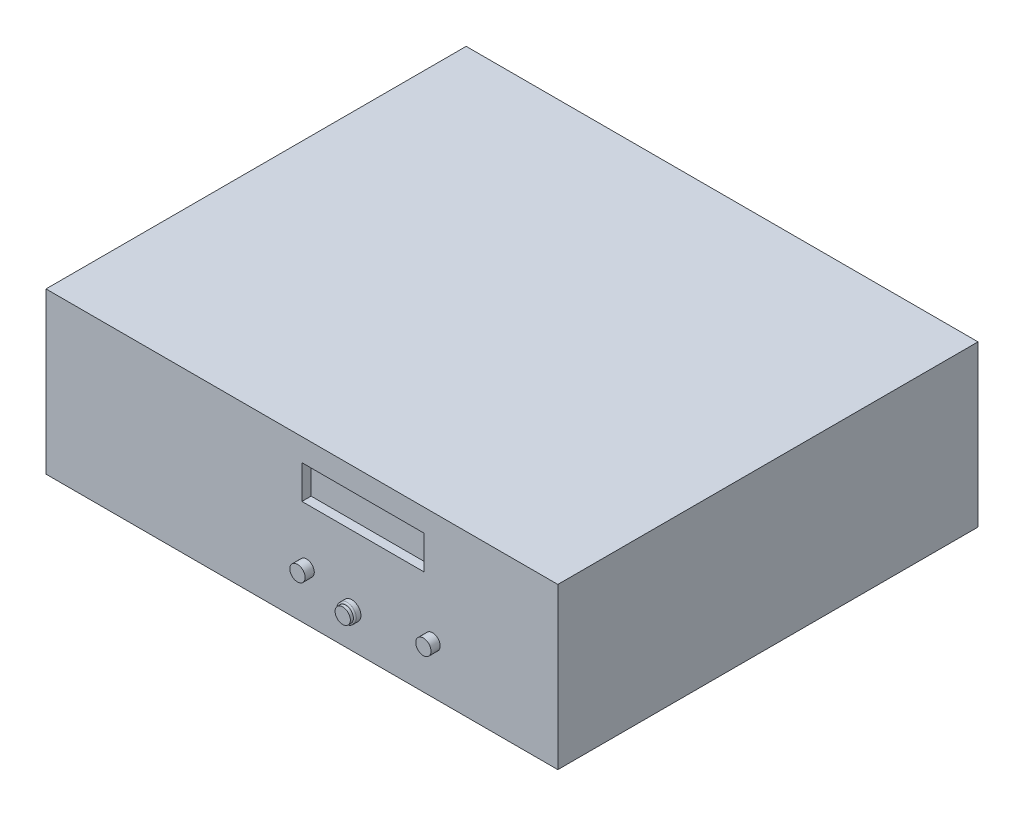
SolidWorks part; units mm, degrees
ref_plane "Front Plane" through (0, 0, 0) normal (0, 0, 1) x (1, 0, 0)
ref_plane "Top Plane" through (0, 0, 0) normal (0, 1, 0) x (1, 0, 0)
ref_plane "Right Plane" through (0, 0, 0) normal (1, 0, 0) x (0, 0, -1)
sketch "Sketch1" plane through (0, 0, 0) normal (0, 1, 0) x (1, 0, 0)
  line L1 (-212.725, -174.625) -> (212.725, -174.625)
  line L2 (-212.725, -174.625) -> (-212.725, 174.625)
  line L3 (-212.725, 174.625) -> (212.725, 174.625)
  line L4 (212.725, -174.625) -> (212.725, 174.625)
  line L5 (-212.725, -174.625) -> (212.725, 174.625) construction
  line L6 (-212.725, 174.625) -> (212.725, -174.625) construction
  point P0 (0, 0)
  dimension "D1" = 425.45
  dimension "D2" = 349.25
extrude "Boss-Extrude1" add sketch "Sketch1" along normal blind 133.35
sketch "Sketch3" plane through (0, 0, 174.625) normal (0, 0, 1) x (1, 0, 0)
  line L1 (0, 86.7356) -> (101.6111, 86.7356)
  line L2 (0, 86.7356) -> (0, 114.6459)
  line L3 (0, 114.6459) -> (101.6111, 114.6459)
  line L4 (101.6111, 86.7356) -> (101.6111, 114.6459)
extrude "Cut-Extrude1" cut sketch "Sketch3" against normal blind 7.62
sketch "Sketch4" plane through (0, 0, 174.625) normal (0, 0, 1) x (1, 0, 0)
  circle A0 centre (3.9249, 40.8754) radius 6.35
  dimension "D1" = 12.7
extrude "Boss-Extrude2" add sketch "Sketch4" along normal blind 7.62
sketch "Sketch5" plane through (0, 0, 174.625) normal (0, 0, 1) x (1, 0, 0)
  circle A0 centre (41.4294, 29.1007) radius 7.62
  dimension "D1" = 15.24
extrude "Boss-Extrude3" add sketch "Sketch5" along normal blind 5.08
fillet "Fillet1" radius 1.27 1 edges at (49.0494, 29.1007, 179.705) conic radius 0.254
sketch "Sketch7" plane through (0, 0, 179.705) normal (0, 0, 1) x (1, 0, 0)
  circle A0 centre (41.5366, 29.0449) radius 6.35
  point P2 (41.5366, 29.0449)
  dimension "D1" = 12.7
extrude "Boss-Extrude4" add sketch "Sketch7" along normal blind 2.54
sketch "Sketch8" plane through (0, 0, 174.625) normal (0, 0, 1) x (1, 0, 0)
  circle A0 centre (108.5887, 40.1644) radius 6.35
  dimension "D1" = 12.7
extrude "Boss-Extrude5" add sketch "Sketch8" along normal blind 7.62
